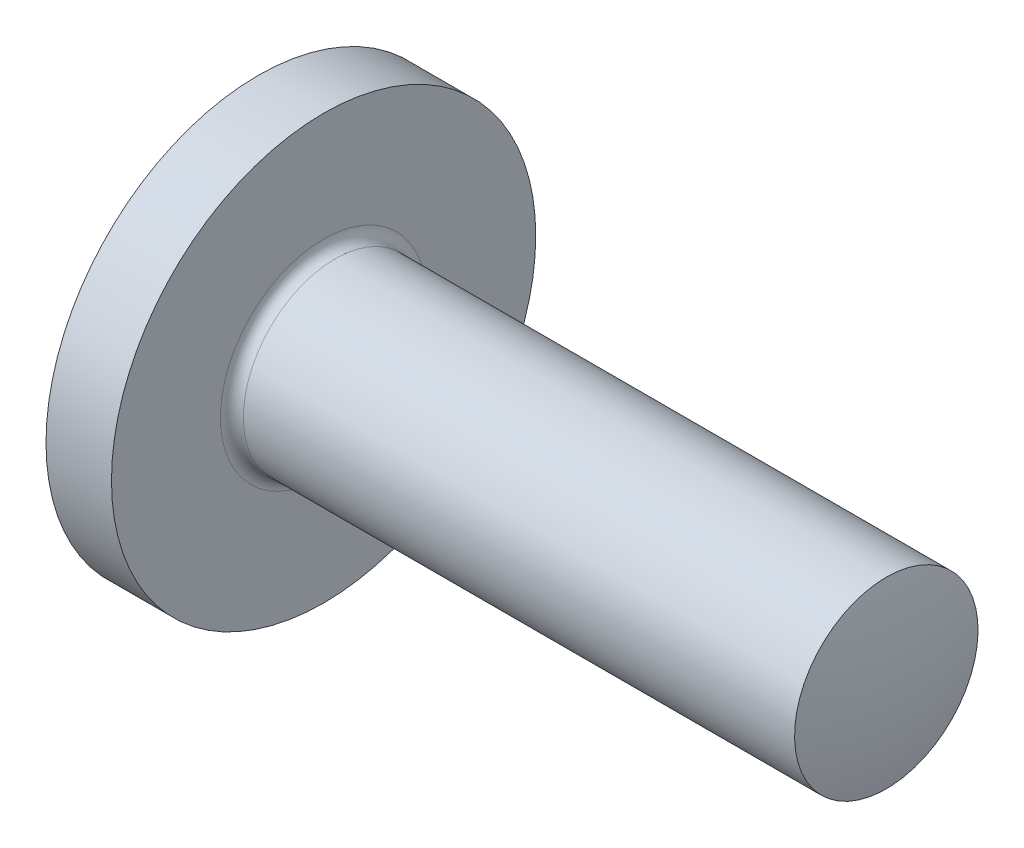
SolidWorks part; units mm, degrees
ref_plane "Front" through (0, 0, 0) normal (0, 0, 1) x (1, 0, 0)
ref_plane "Top" through (0, 0, 0) normal (0, 1, 0) x (1, 0, 0)
ref_plane "Right" through (0, 0, 0) normal (1, 0, 0) x (0, 0, -1)
sketch "Sketch1" plane through (0, 0, 0) normal (1, 0, 0) x (0, 0, -1)
  circle A0 centre (0, 0) radius 1.85
extrude "BaseHead" add sketch "Sketch1" along normal blind 1.1
sketch "Sketch2" plane through (1.1, 0.0676, 0.3015) normal (1, 0, 0) x (0, 0, -1)
  line L0 (0.3015, -0.0676) -> (1.3015, -0.0676) construction
  circle A0 centre (0.3015, -0.0676) radius 0.8
  circle A1 centre (0.3015, -0.0676) radius 1.85 construction
extrude "BaseBody" add sketch "Sketch2" along normal blind 5
cosmetic thread "ThreadCosmetic1" [suppressed] parameters "D1"=4, "D2"=1.2
sketch "Sketch3" plane through (0, 0, 0) normal (0, 0, 1) x (1, 0, 0)
  line L1 (0, 0.25) -> (0.5, 0.25)
  line L2 (0, 0.25) -> (0, -0.25)
  line L3 (0, -0.25) -> (0.5, -0.25)
  line L4 (0.5, 0.25) -> (0.5, -0.25)
  line L5 (0, 1.85) -> (0, -1.85) construction
  dimension "m" = 0.25
extrude "Slot" cut sketch "Sketch3" against normal through all and the other way through all
sketch "Sketch4" plane through (-5.7638, 3.9138, 0) normal (0, 0, 1) x (0, -1, 0)
  line L0 (3.9138, 15.0989) -> (3.9138, -3.5713) construction
  line L1 (3.1138, 11.8638) -> (3.1138, 6.8638) construction
  line L2 (2.0638, 6.8638) -> (2.0638, 5.7638) construction
  line L4 (3.1138, 13.8638) -> (3.1138, 11.7711)
  line L5 (3.9138, 11.8638) -> (3.9138, 13.8638)
  line L6 (3.9138, 13.8638) -> (3.1138, 13.8638)
  line L8 (2.0638, 3.7638) -> (3.9138, 3.7638)
  line L9 (3.9138, 3.7638) -> (3.9138, 5.7638)
  line L10 (2.0638, 6.2927) -> (2.0638, 3.7638)
  line L11 (2.0638, 5.7638) -> (3.6638, 5.7638) construction
  line L13 (4.7138, 11.8638) -> (3.1138, 11.8638) construction
  arc A0 (2.0638, 6.2927) -> (3.9138, 5.7638) centre (3.9138, 9.2638) ccw
  arc A1 (3.9138, 11.8638) -> (3.1138, 11.7711) centre (3.9138, 8.3638) ccw
  dimension "re" = 3.5
  dimension "D2" = 2
  dimension "D3" = 2
revolve "BaseTop" cut sketch "Sketch4" angle 360 about L0
fillet "HeadFillet" radius 0.1 1 edges at (1.1, 0, -0.8)
sketch "Sketch5" plane through (0, 0, 0) normal (0, 0, 1) x (1, 0, 0)
  line L0 (6.0073, 0.6268) -> (6.1073, 0.8)
  line L1 (6.1073, 0.8) -> (6.1073, 1)
  line L2 (6.1073, 1) -> (5.9073, 1)
  line L3 (5.9073, 1) -> (5.9073, 0.8)
  line L4 (5.9073, 0.8) -> (6.0073, 0.6268)
  line L5 (6.0073, 0.8) -> (6.0073, -0.8) construction
  line L6 (0, 0) -> (7.0548, 0) construction
  dimension "D1" = 1.6
  dimension "D2" = 0.2
revolve "Cut-Revolve10" [suppressed] cut sketch "Sketch5" angle 360 about L6
pattern_linear "LPattern10" [suppressed] count 17 spacing 0.24 along (-1, 0, 0) of bodies 105
equation "\"m@Sketch3\" =\"n@Sketch3\" / 2"
equation "\"D1@ThreadCosmetic1\" = \"l@BaseBody\" -\"a@Sketch2\""
equation "\"D1@Sketch5\" = \"d@Sketch2\""
equation "\"D2@Sketch5\" =  ( \"d@Sketch2\" - \"D2@ThreadCosmetic1\" )  / 2"
equation "\"D3@LPattern10\" = \"D2@Sketch5\" * 1.2"
equation "\"D1@LPattern10\" = \"D1@ThreadCosmetic1\" / \"D3@LPattern10\""
